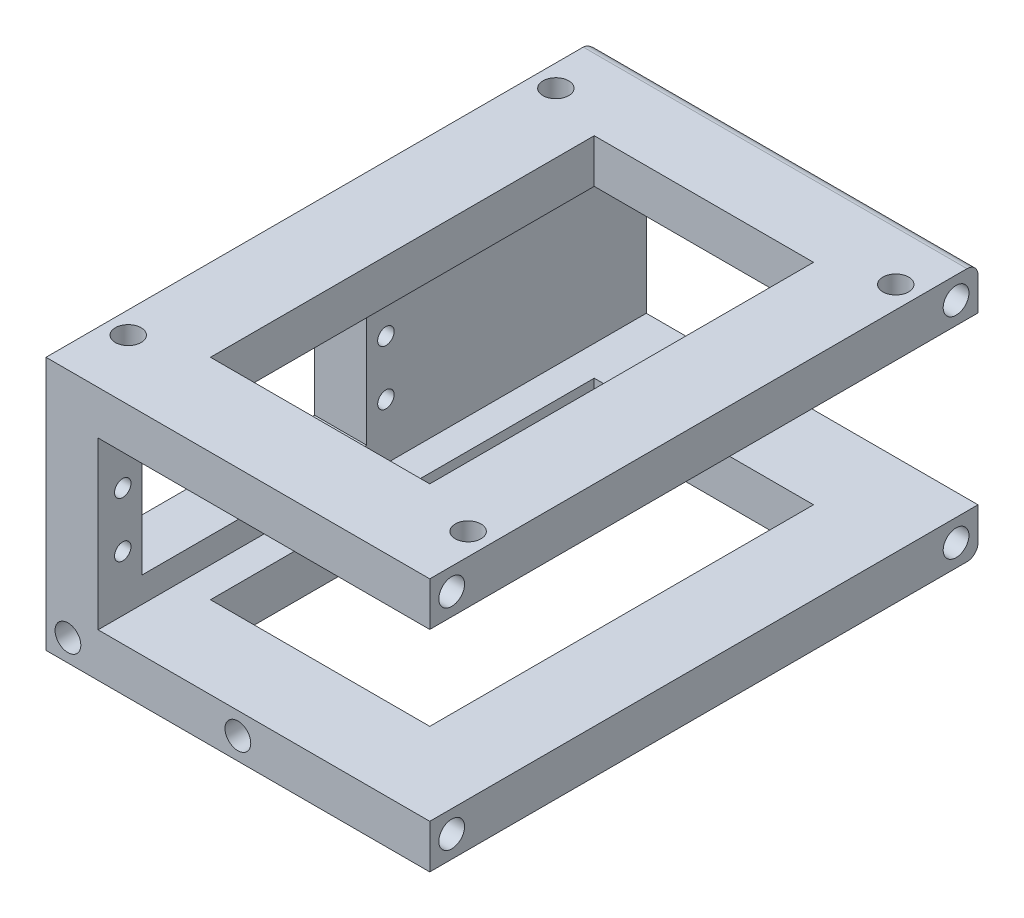
SolidWorks part; units mm, degrees
ref_plane "Front Plane" through (0, 0, 0) normal (0, 0, 1) x (1, 0, 0)
ref_plane "Top Plane" through (0, 0, 0) normal (0, 1, 0) x (1, 0, 0)
ref_plane "Right Plane" through (0, 0, 0) normal (1, 0, 0) x (0, 0, -1)
sketch "Sketch1" plane through (0, 0, 0) normal (0, 0, 1) x (1, 0, 0)
  line L0 (0, 46.3) -> (0, 0)
  line L1 (0, 0) -> (70, 0)
  line L2 (70, 0) -> (70, 8)
  line L3 (70, 8) -> (9.5, 8)
  line L4 (9.5, 8) -> (9.5, 38.3)
  line L5 (9.5, 38.3) -> (70, 38.3)
  line L6 (70, 38.3) -> (70, 46.3)
  line L7 (70, 46.3) -> (0, 46.3)
  dimension "D1" = 46.3
  dimension "D2" = 70
  dimension "D3" = 9.5
  dimension "D4" = 8
  dimension "D5" = 8
extrude "Boss-Extrude1" add sketch "Sketch1" along normal blind 100
sketch "Sketch2" plane through (0, 0, 0) normal (0, -1, 0) x (1, 0, 0)
  line L0 (70, 100) -> (70, 0) construction
  line L1 (15, 15) -> (55, 15)
  line L2 (15, 15) -> (15, 85)
  line L3 (15, 85) -> (55, 85)
  line L4 (55, 15) -> (55, 85)
  line L5 (15, 15) -> (55, 85) construction
  line L6 (15, 85) -> (55, 15) construction
  line L7 (0, 100) -> (70, 100) construction
  point P0 (35, 50)
  dimension "D1" = 40
  dimension "D2" = 35
  dimension "D3" = 50
  dimension "D4" = 70
extrude "Cut-Extrude1" cut sketch "Sketch2" against normal blind 100
sketch "Sketch3" plane through (70, 0, 0) normal (1, 0, 0) x (0, 0, -1)
  line L0 (0, 23.15) -> (-100, 23.15) construction
  line L1 (0, 8) -> (0, 38.3) construction
  line L2 (-100, 8) -> (-100, 38.3) construction
  line L3 (-50, 0) -> (-50, 46.3) construction
  line L4 (-100, 0) -> (0, 0) construction
  line L5 (-100, 46.3) -> (0, 46.3) construction
  line L6 (-100, 38.3) -> (-100, 46.3) construction
  circle A0 centre (-96, 42.3) radius 2.35
  circle A1 centre (-4, 42.3) radius 2.35
  circle A2 centre (-4, 4) radius 2.35
  circle A3 centre (-96, 4) radius 2.35
  dimension "D1" = 4.7
  dimension "D2" = 4
  dimension "D3" = 4
extrude "Cut-Extrude2" cut sketch "Sketch3" against normal blind 6
sketch "Sketch4" plane through (9.5, 0, 0) normal (1, 0, 0) x (0, 0, -1)
  line L0 (-92, 23.15) -> (-51, 23.15) construction
  line L5 (-92, 12.65) -> (-51, 12.65)
  line L6 (-92, 12.65) -> (-92, 33.65)
  line L7 (-92, 33.65) -> (-51, 33.65)
  line L8 (-51, 12.65) -> (-51, 33.65)
  line L9 (-71.5, 12.65) -> (-71.5, 33.65) construction
  line L13 (-100, 38.3) -> (0, 38.3) construction
  line L14 (-100, 8) -> (-100, 38.3) construction
  circle A4 centre (-95.5, 28.15) radius 1.5
  circle A5 centre (-95.5, 18.15) radius 1.5
  circle A6 centre (-47.5, 18.15) radius 1.5
  circle A7 centre (-47.5, 28.15) radius 1.5
  dimension "D3" = 24
  dimension "D5" = 3
  dimension "D1" = 21
  dimension "D2" = 41
  dimension "D4" = 5
  dimension "D6" = 15.15
  dimension "D7" = 8
extrude "Cut-Extrude3" cut sketch "Sketch4" against normal up to next
sketch "Sketch5" plane through (0, 46.3, 0) normal (0, 1, 0) x (1, 0, 0)
  line L0 (35, -100) -> (35, -83.0939) construction
  line L1 (70, -100) -> (0, -100) construction
  line L3 (0, -100) -> (0, 0) construction
  line L4 (55, -85) -> (15, -85) construction
  line L5 (0, -50) -> (70, -50) construction
  line L6 (70, -100) -> (70, 0) construction
  circle A1 centre (4, -89) radius 2.35
  circle A3 centre (66, -89) radius 2.35
  circle A4 centre (66, -11) radius 2.35
  circle A5 centre (4, -11) radius 2.35
  dimension "D1" = 4.7
  dimension "D3" = 4
  dimension "D2" = 4
extrude "Cut-Extrude4" cut sketch "Sketch5" against normal blind 6
sketch "Sketch6" plane through (0, 0, 100) normal (0, 0, 1) x (1, 0, 0)
  line L1 (0, 0) -> (70, 0) construction
  line L2 (0, 46.3) -> (0, 0) construction
  line L3 (70, 8) -> (9.5, 8) construction
  circle A0 centre (4, 4) radius 2.35
  circle A1 centre (35, 4) radius 2.35
  dimension "D1" = 4.7
  dimension "D2" = 4
  dimension "D3" = 4
  dimension "D4" = 4.7
  dimension "D5" = 4
  dimension "D6" = 35
extrude "Cut-Extrude5" cut sketch "Sketch6" against normal blind 6
sketch "Sketch7" plane through (0, 0, 0) normal (0, 0, -1) x (-1, 0, 0)
  line L0 (0, 46.3) -> (0, 0) construction
  line L1 (0, 0) -> (-70, 0) construction
  circle A0 centre (-35, 4) radius 2.35
  circle A1 centre (-4, 4) radius 2.35
  dimension "D1" = 4.7
  dimension "D2" = 4.7
  dimension "D6" = 4
  dimension "D3" = 4
  dimension "D4" = 4
  dimension "D5" = 35
extrude "Cut-Extrude6" cut sketch "Sketch7" against normal blind 6
fillet "Fillet2" radius 2 3 edges at (0, 23.15, 0) (35, 46.3, 0) (35, 0, 0)
